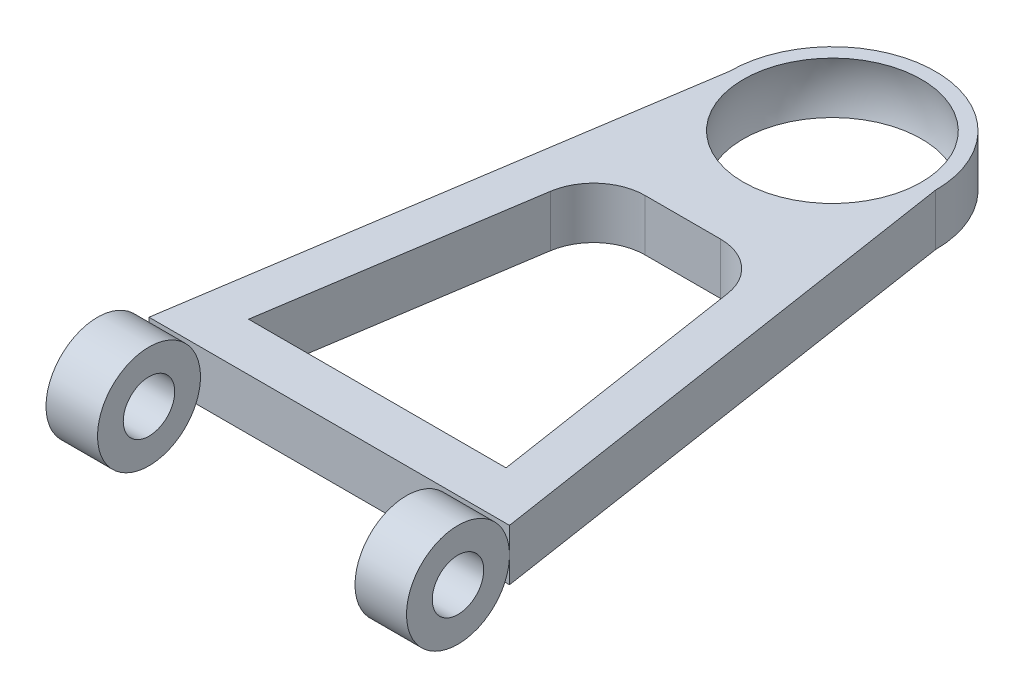
SolidWorks part; units mm, degrees
material "201 Annealed Stainless Steel (SS)"
ref_plane "Front Plane" through (0, 0, 0) normal (0, 0, 1) x (1, 0, 0)
ref_plane "Top Plane" through (0, 0, 0) normal (0, 1, 0) x (1, 0, 0)
ref_plane "Right Plane" through (0, 0, 0) normal (1, 0, 0) x (0, 0, -1)
sketch "Sketch2" plane through (0, 0, 0) normal (0, 1, 0) x (1, 0, 0)
  line L0 (-35, 0) -> (35, 0)
  line L1 (0, 0) -> (0, 97.7) construction
  line L2 (-35, 0) -> (-20, 97.7)
  line L3 (35, 0) -> (20, 97.7)
  circle A0 centre (0, 97.7) radius 18
  circle A1 centre (0, 97.7) radius 20
  point P4 (0, 0)
extrude "Boss-Extrude1" add sketch "Sketch2" along normal blind 5 and the other way blind 5 contours L1 L0 L3 A1 | L0 L1 A1 L2 | A1 region at (-14.8328, 0, -38.4767) region at (14.8328, 0, -38.4767)
sketch "Sketch3" plane through (0, 0, 0) normal (0, 1, 0) x (1, 0, 0)
  line L1 (-35, 0) -> (-25, 0)
  line L2 (-35, 0) -> (-35, -10)
  line L3 (-35, -10) -> (-25, -10)
  line L4 (-25, 0) -> (-25, -10)
  line L5 (35, 0) -> (25, 0)
  line L6 (35, 0) -> (35, -10)
  line L7 (35, -10) -> (25, -10)
  line L8 (25, 0) -> (25, -10)
  dimension "D1" = 10
  dimension "D2" = 10
  dimension "D3" = 10
  dimension "D4" = 10
revolve "Revolve2" add sketch "Sketch3" angle 360 about L3
sketch "Sketch5" plane through (35, 0, 0) normal (1, 0, 0) x (0, 0, -1)
  circle A0 centre (-10, 0) radius 5
extrude "Cut-Extrude2" cut sketch "Sketch5" against normal blind 98
sketch "Sketch7" plane through (0, 5, 0) normal (0, 1, 0) x (1, 0, 0)
  line L0 (0, 9.3323) -> (25, 9.3323)
  line L1 (0, 9.3323) -> (-25, 9.3323)
  line L2 (-25, 9.3323) -> (-17.1971, 60.155)
  line L3 (-35, 0) -> (-20, 97.7) construction
  line L4 (25, 9.3323) -> (17.1971, 60.155)
  line L5 (35, 0) -> (20, 97.7) construction
  line L6 (-7.313, 68.6374) -> (7.313, 68.6374)
  arc A0 (17.1971, 60.155) -> (7.313, 68.6374) centre (7.313, 58.6374) ccw
  arc A1 (-17.1971, 60.155) -> (-7.313, 68.6374) centre (-7.313, 58.6374) cw
  dimension "D1" = 10
extrude "Cut-Extrude4" cut sketch "Sketch7" against normal blind 98
sketch "Sketch9" plane through (0, 0, 0) normal (0, 1, 0) x (1, 0, 0)
  line L0 (-18, 97.7) -> (18, 97.7)
  arc A0 (18, 97.7) -> (-18, 97.7) centre (0, 97.7) ccw
revolve "Cut-Revolve1" cut sketch "Sketch9" angle 360 about L0
